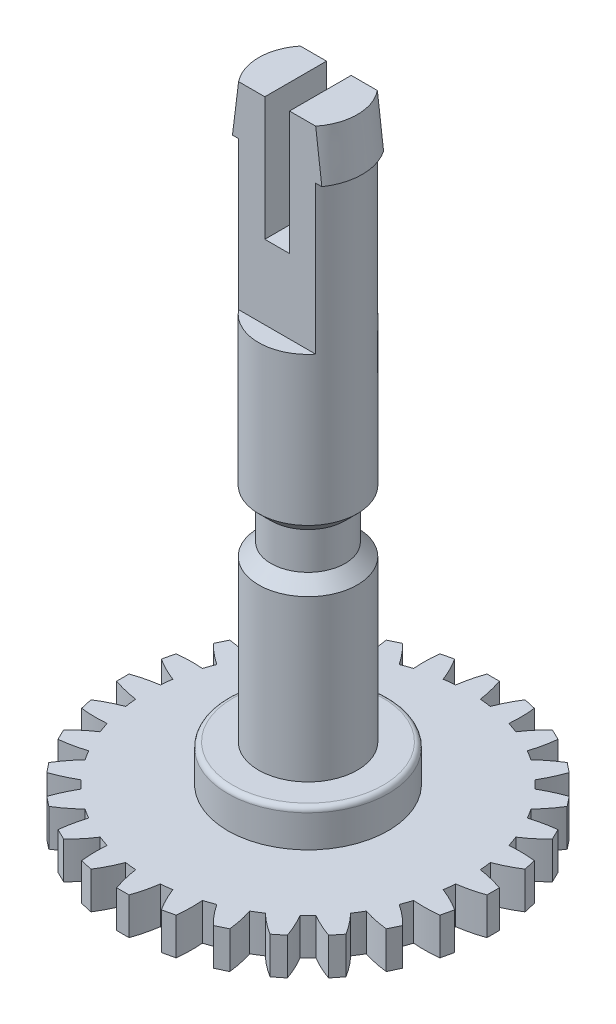
SolidWorks part; units mm, degrees
ref_plane "前视基准面" through (0, 0, 0) normal (0, 0, 1) x (1, 0, 0)
ref_plane "上视基准面" through (0, 0, 0) normal (0, 1, 0) x (1, 0, 0)
ref_plane "右视基准面" through (0, 0, 0) normal (1, 0, 0) x (0, 0, -1)
sketch "草图1" plane through (0, 0, 0) normal (0, 1, 0) x (1, 0, 0)
  circle A0 centre (0, 0) radius 6.5
extrude "凸台-拉伸1" add sketch "草图1" along normal blind 1.5
sketch "草图2" plane through (0, 1.5, 0) normal (0, 1, 0) x (-1, 0, 0)
  circle A0 centre (0, 0) radius 3.25
extrude "凸台-拉伸2" add sketch "草图2" along normal blind 1.5
sketch "草图3" plane through (0, 3, 0) normal (0, 1, 0) x (-1, 0, 0)
  circle A0 centre (0, 0) radius 2
extrude "凸台-拉伸3" add sketch "草图3" along normal blind 23
sketch "草图4" plane through (0, 1.5, 0) normal (0, 1, 0) x (-1, 0, 0)
  circle A0 centre (0, 0) radius 2
  circle A1 centre (0, 0) radius 1.5
extrude "切除-拉伸1" cut sketch "草图4" along normal blind 1.5 from offset 8.5
sketch "草图5" plane through (0, 0, 0) normal (0, 0, 1) x (1, 0, 0)
  line L1 (0, 26) -> (0, 24)
  line L2 (2, 26) -> (-2, 26) construction
  line L3 (0, 24) -> (2.2, 24)
  line L4 (2.2, 24) -> (2, 26)
  line L5 (2, 26) -> (0, 26)
  dimension "D1" = 2.2
  dimension "D2" = 2
revolve "旋转1" add sketch "草图5" angle 360 about L1
sketch "草图6" plane through (0, 26, 0) normal (0, 1, 0) x (-1, 0, 0)
  line L1 (2.1, -1.25) -> (-2.1, -1.25)
  line L2 (2.1, -1.25) -> (2.1, -2.25)
  line L3 (2.1, -2.25) -> (-2.1, -2.25)
  line L4 (-2.1, -1.25) -> (-2.1, -2.25)
  line L5 (2.1, 1.25) -> (-2.1, 1.25)
  line L6 (2.1, 1.25) -> (2.1, 2.25)
  line L7 (2.1, 2.25) -> (-2.1, 2.25)
  line L8 (-2.1, 1.25) -> (-2.1, 2.25)
  dimension "D1" = 1.25
  dimension "D2" = 1.25
  dimension "D3" = 1
  dimension "D4" = 1
extrude "切除-拉伸2" cut sketch "草图6" against normal blind 8
sketch "草图7" plane through (0, 0, 1.25) normal (0, 0, 1) x (1, 0, 0)
  line L0 (1.5612, 26) -> (-1.5612, 26) construction
  line L1 (-0.5, 26) -> (0.5, 26)
  line L2 (-0.5, 26) -> (-0.5, 21)
  line L3 (-0.5, 21) -> (0.5, 21)
  line L4 (0.5, 26) -> (0.5, 21)
extrude "切除-拉伸3" cut sketch "草图7" against normal up to next
chamfer "倒角1" distance 0.5 angle 45 2 edges at (0, 10, 2) (0, 11.5, 2)
fillet "圆角1" radius 0.2 1 edges at (0, 3, 3.25)
sketch "草图9" plane through (0, 0, 0) normal (0, -1, 0) x (1, 0, 0)
  line L0 (1.4252, 7.3676) -> (1.9126, 7.2563)
  line L1 (-0.25, 7.5) -> (0.25, 7.5)
  line L2 (3.0289, 6.8657) -> (3.4794, 6.6488)
  line L3 (4.4807, 6.0196) -> (4.8716, 5.7079)
  line L4 (5.7079, 4.8716) -> (6.0196, 4.4807)
  line L5 (6.6488, 3.4794) -> (6.8657, 3.0289)
  line L6 (7.2563, 1.9126) -> (7.3676, 1.4252)
  line L7 (7.5, 0.25) -> (7.5, -0.25)
  line L8 (7.3676, -1.4252) -> (7.2563, -1.9126)
  line L9 (6.8657, -3.0289) -> (6.6488, -3.4794)
  line L10 (6.0196, -4.4807) -> (5.7079, -4.8716)
  line L11 (4.8716, -5.7079) -> (4.4807, -6.0196)
  line L12 (3.4794, -6.6488) -> (3.0289, -6.8657)
  line L13 (1.9126, -7.2563) -> (1.4252, -7.3676)
  line L14 (0.25, -7.5) -> (-0.25, -7.5)
  line L15 (-1.4252, -7.3676) -> (-1.9126, -7.2563)
  line L16 (-3.0289, -6.8657) -> (-3.4794, -6.6488)
  line L17 (-4.4807, -6.0196) -> (-4.8716, -5.7079)
  line L18 (-5.7079, -4.8716) -> (-6.0196, -4.4807)
  line L19 (-6.6488, -3.4794) -> (-6.8657, -3.0289)
  line L20 (-7.2563, -1.9126) -> (-7.3676, -1.4252)
  line L21 (-7.5, -0.25) -> (-7.5, 0.25)
  line L22 (-7.3676, 1.4252) -> (-7.2563, 1.9126)
  line L23 (-6.8657, 3.0289) -> (-6.6488, 3.4794)
  line L24 (-6.0196, 4.4807) -> (-5.7079, 4.8716)
  line L25 (-4.8716, 5.7079) -> (-4.4807, 6.0196)
  line L26 (-3.4794, 6.6488) -> (-3.0289, 6.8657)
  line L27 (-1.9126, 7.2563) -> (-1.4252, 7.3676)
  arc A0 (0.5, 6.4807) -> (-0.5, 6.4807) centre (0, 0) ccw
  arc A1 (0.5, 6.4807) -> (0.25, 7.5) centre (-4.6435, 5.7595) ccw
  arc A2 (-0.5, 6.4807) -> (-0.25, 7.5) centre (4.6435, 5.7595) cw
  arc A3 (1.9296, 6.207) -> (0.9546, 6.4295) centre (0, 0) ccw
  arc A4 (1.9296, 6.207) -> (1.9126, 7.2563) centre (-3.2454, 6.6483) ccw
  arc A5 (0.9546, 6.4295) -> (1.4252, 7.3676) centre (5.8086, 4.5818) cw
  arc A6 (3.2624, 5.622) -> (2.3614, 6.0559) centre (0, 0) ccw
  arc A7 (3.2624, 5.622) -> (3.4794, 6.6488) centre (-1.6847, 7.2038) ccw
  arc A8 (2.3614, 6.0559) -> (3.0289, 6.8657) centre (6.6826, 3.1744) cw
  arc A9 (4.4316, 4.7551) -> (3.6498, 5.3786) centre (0, 0) ccw
  arc A10 (4.4316, 4.7551) -> (4.8716, 5.7079) centre (-0.0394, 7.3981) ccw
  arc A11 (3.6498, 5.3786) -> (4.4807, 6.0196) centre (7.2214, 1.6078) cw
  arc A12 (5.3786, 3.6498) -> (4.7551, 4.4316) centre (0, 0) ccw
  arc A13 (5.3786, 3.6498) -> (6.0196, 4.4807) centre (1.6078, 7.2214) ccw
  arc A14 (4.7551, 4.4316) -> (5.7079, 4.8716) centre (7.3981, -0.0394) cw
  arc A15 (6.0559, 2.3614) -> (5.622, 3.2624) centre (0, 0) ccw
  arc A16 (6.0559, 2.3614) -> (6.8657, 3.0289) centre (3.1744, 6.6826) ccw
  arc A17 (5.622, 3.2624) -> (6.6488, 3.4794) centre (7.2038, -1.6847) cw
  arc A18 (6.4295, 0.9546) -> (6.207, 1.9296) centre (0, 0) ccw
  arc A19 (6.4295, 0.9546) -> (7.3676, 1.4252) centre (4.5818, 5.8086) ccw
  arc A20 (6.207, 1.9296) -> (7.2563, 1.9126) centre (6.6483, -3.2454) cw
  arc A21 (6.4807, -0.5) -> (6.4807, 0.5) centre (0, 0) ccw
  arc A22 (6.4807, -0.5) -> (7.5, -0.25) centre (5.7595, 4.6435) ccw
  arc A23 (6.4807, 0.5) -> (7.5, 0.25) centre (5.7595, -4.6435) cw
  arc A24 (6.207, -1.9296) -> (6.4295, -0.9546) centre (0, 0) ccw
  arc A25 (6.207, -1.9296) -> (7.2563, -1.9126) centre (6.6483, 3.2454) ccw
  arc A26 (6.4295, -0.9546) -> (7.3676, -1.4252) centre (4.5818, -5.8086) cw
  arc A27 (5.622, -3.2624) -> (6.0559, -2.3614) centre (0, 0) ccw
  arc A28 (5.622, -3.2624) -> (6.6488, -3.4794) centre (7.2038, 1.6847) ccw
  arc A29 (6.0559, -2.3614) -> (6.8657, -3.0289) centre (3.1744, -6.6826) cw
  arc A30 (4.7551, -4.4316) -> (5.3786, -3.6498) centre (0, 0) ccw
  arc A31 (4.7551, -4.4316) -> (5.7079, -4.8716) centre (7.3981, 0.0394) ccw
  arc A32 (5.3786, -3.6498) -> (6.0196, -4.4807) centre (1.6078, -7.2214) cw
  arc A33 (3.6498, -5.3786) -> (4.4316, -4.7551) centre (0, 0) ccw
  arc A34 (3.6498, -5.3786) -> (4.4807, -6.0196) centre (7.2214, -1.6078) ccw
  arc A35 (4.4316, -4.7551) -> (4.8716, -5.7079) centre (-0.0394, -7.3981) cw
  arc A36 (2.3614, -6.0559) -> (3.2624, -5.622) centre (0, 0) ccw
  arc A37 (2.3614, -6.0559) -> (3.0289, -6.8657) centre (6.6826, -3.1744) ccw
  arc A38 (3.2624, -5.622) -> (3.4794, -6.6488) centre (-1.6847, -7.2038) cw
  arc A39 (0.9546, -6.4295) -> (1.9296, -6.207) centre (0, 0) ccw
  arc A40 (0.9546, -6.4295) -> (1.4252, -7.3676) centre (5.8086, -4.5818) ccw
  arc A41 (1.9296, -6.207) -> (1.9126, -7.2563) centre (-3.2454, -6.6483) cw
  arc A42 (-0.5, -6.4807) -> (0.5, -6.4807) centre (0, 0) ccw
  arc A43 (-0.5, -6.4807) -> (-0.25, -7.5) centre (4.6435, -5.7595) ccw
  arc A44 (0.5, -6.4807) -> (0.25, -7.5) centre (-4.6435, -5.7595) cw
  arc A45 (-1.9296, -6.207) -> (-0.9546, -6.4295) centre (0, 0) ccw
  arc A46 (-1.9296, -6.207) -> (-1.9126, -7.2563) centre (3.2454, -6.6483) ccw
  arc A47 (-0.9546, -6.4295) -> (-1.4252, -7.3676) centre (-5.8086, -4.5818) cw
  arc A48 (-3.2624, -5.622) -> (-2.3614, -6.0559) centre (0, 0) ccw
  arc A49 (-3.2624, -5.622) -> (-3.4794, -6.6488) centre (1.6847, -7.2038) ccw
  arc A50 (-2.3614, -6.0559) -> (-3.0289, -6.8657) centre (-6.6826, -3.1744) cw
  arc A51 (-4.4316, -4.7551) -> (-3.6498, -5.3786) centre (0, 0) ccw
  arc A52 (-4.4316, -4.7551) -> (-4.8716, -5.7079) centre (0.0394, -7.3981) ccw
  arc A53 (-3.6498, -5.3786) -> (-4.4807, -6.0196) centre (-7.2214, -1.6078) cw
  arc A54 (-5.3786, -3.6498) -> (-4.7551, -4.4316) centre (0, 0) ccw
  arc A55 (-5.3786, -3.6498) -> (-6.0196, -4.4807) centre (-1.6078, -7.2214) ccw
  arc A56 (-4.7551, -4.4316) -> (-5.7079, -4.8716) centre (-7.3981, 0.0394) cw
  arc A57 (-6.0559, -2.3614) -> (-5.622, -3.2624) centre (0, 0) ccw
  arc A58 (-6.0559, -2.3614) -> (-6.8657, -3.0289) centre (-3.1744, -6.6826) ccw
  arc A59 (-5.622, -3.2624) -> (-6.6488, -3.4794) centre (-7.2038, 1.6847) cw
  arc A60 (-6.4295, -0.9546) -> (-6.207, -1.9296) centre (0, 0) ccw
  arc A61 (-6.4295, -0.9546) -> (-7.3676, -1.4252) centre (-4.5818, -5.8086) ccw
  arc A62 (-6.207, -1.9296) -> (-7.2563, -1.9126) centre (-6.6483, 3.2454) cw
  arc A63 (-6.4807, 0.5) -> (-6.4807, -0.5) centre (0, 0) ccw
  arc A64 (-6.4807, 0.5) -> (-7.5, 0.25) centre (-5.7595, -4.6435) ccw
  arc A65 (-6.4807, -0.5) -> (-7.5, -0.25) centre (-5.7595, 4.6435) cw
  arc A66 (-6.207, 1.9296) -> (-6.4295, 0.9546) centre (0, 0) ccw
  arc A67 (-6.207, 1.9296) -> (-7.2563, 1.9126) centre (-6.6483, -3.2454) ccw
  arc A68 (-6.4295, 0.9546) -> (-7.3676, 1.4252) centre (-4.5818, 5.8086) cw
  arc A69 (-5.622, 3.2624) -> (-6.0559, 2.3614) centre (0, 0) ccw
  arc A70 (-5.622, 3.2624) -> (-6.6488, 3.4794) centre (-7.2038, -1.6847) ccw
  arc A71 (-6.0559, 2.3614) -> (-6.8657, 3.0289) centre (-3.1744, 6.6826) cw
  arc A72 (-4.7551, 4.4316) -> (-5.3786, 3.6498) centre (0, 0) ccw
  arc A73 (-4.7551, 4.4316) -> (-5.7079, 4.8716) centre (-7.3981, -0.0394) ccw
  arc A74 (-5.3786, 3.6498) -> (-6.0196, 4.4807) centre (-1.6078, 7.2214) cw
  arc A75 (-3.6498, 5.3786) -> (-4.4316, 4.7551) centre (0, 0) ccw
  arc A76 (-3.6498, 5.3786) -> (-4.4807, 6.0196) centre (-7.2214, 1.6078) ccw
  arc A77 (-4.4316, 4.7551) -> (-4.8716, 5.7079) centre (0.0394, 7.3981) cw
  arc A78 (-2.3614, 6.0559) -> (-3.2624, 5.622) centre (0, 0) ccw
  arc A79 (-2.3614, 6.0559) -> (-3.0289, 6.8657) centre (-6.6826, 3.1744) ccw
  arc A80 (-3.2624, 5.622) -> (-3.4794, 6.6488) centre (1.6847, 7.2038) cw
  arc A81 (-0.9546, 6.4295) -> (-1.9296, 6.207) centre (0, 0) ccw
  arc A82 (-0.9546, 6.4295) -> (-1.4252, 7.3676) centre (-5.8086, 4.5818) ccw
  arc A83 (-1.9296, 6.207) -> (-1.9126, 7.2563) centre (3.2454, 6.6483) cw
  point P5 (0, 7.5)
  point P13 (1.6689, 7.312)
  point P21 (3.2541, 6.7573)
  point P29 (4.6762, 5.8637)
  point P37 (5.8637, 4.6762)
  point P45 (6.7573, 3.2541)
  point P53 (7.312, 1.6689)
  point P61 (7.5, 0)
  point P69 (7.312, -1.6689)
  point P77 (6.7573, -3.2541)
  point P85 (5.8637, -4.6762)
  point P93 (4.6762, -5.8637)
  point P101 (3.2541, -6.7573)
  point P109 (1.6689, -7.312)
  point P117 (0, -7.5)
  point P125 (-1.6689, -7.312)
  point P133 (-3.2541, -6.7573)
  point P141 (-4.6762, -5.8637)
  point P149 (-5.8637, -4.6762)
  point P157 (-6.7573, -3.2541)
  point P165 (-7.312, -1.6689)
  point P173 (-7.5, 0)
  point P181 (-7.312, 1.6689)
  point P189 (-6.7573, 3.2541)
  point P197 (-5.8637, 4.6762)
  point P205 (-4.6762, 5.8637)
  point P213 (-3.2541, 6.7573)
  point P221 (-1.6689, 7.312)
  dimension "D1" = 28
extrude "凸台-拉伸4" add sketch "草图9" against normal up to surface (1.5 mm away) up to face at (0, 1.5, 6.5)
sketch "草图10" plane through (0, 0, 0) normal (0, 0, 1) x (1, 0, 0)
  line L0 (0, 0) -> (2.25, 0)
  line L1 (0, 0) -> (0, 1)
  line L2 (0, 1) -> (2.25, 0)
revolve "切除-旋转2" cut sketch "草图10" angle 360 about L1
